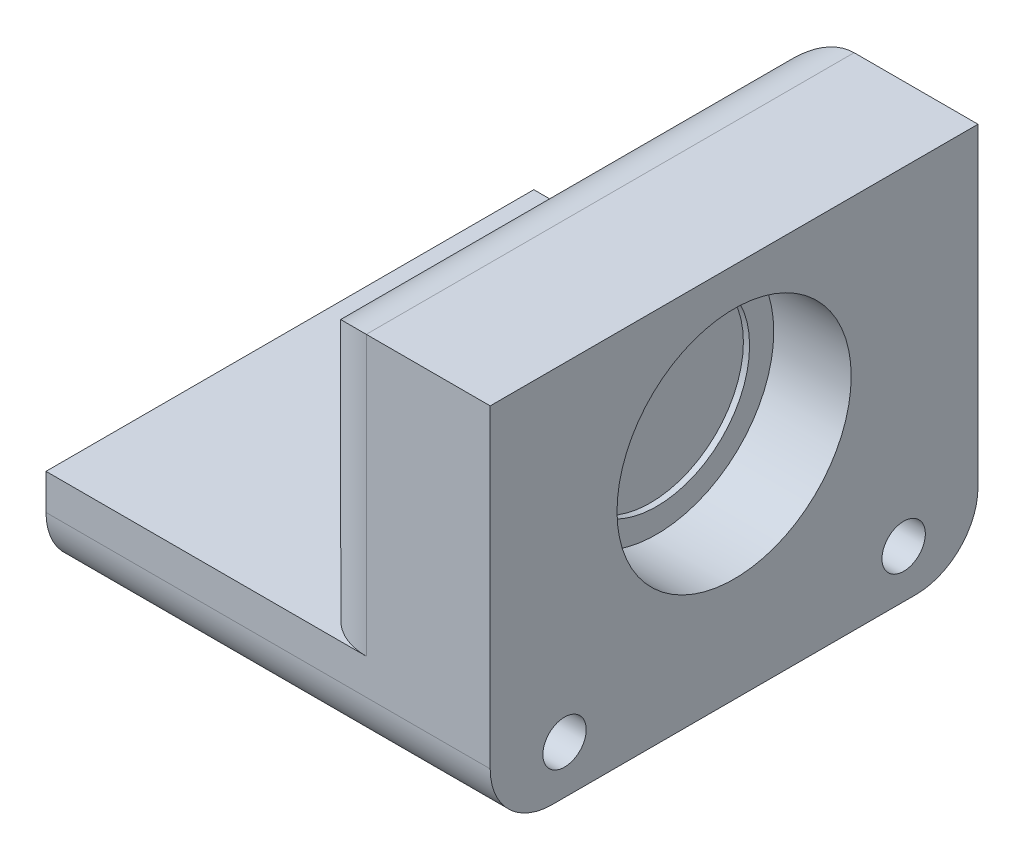
SolidWorks part; units mm, degrees
ref_plane "Front Plane" through (0, 0, 0) normal (0, 0, 1) x (1, 0, 0)
ref_plane "Top Plane" through (0, 0, 0) normal (0, 1, 0) x (1, 0, 0)
ref_plane "Right Plane" through (0, 0, 0) normal (1, 0, 0) x (0, 0, -1)
sketch "Sketch1" plane through (0, 0, 0) normal (0, 0, 1) x (1, 0, 0)
  line L0 (-71.7423, 0) -> (-71.7423, -4)
  line L1 (-71.7423, -4) -> (-53.5305, -4)
  line L2 (-53.5305, -4) -> (-53.5305, 11.43)
  line L3 (-53.5305, 11.43) -> (-61.1505, 11.43)
  line L4 (-61.1505, 11.43) -> (-61.1505, 0)
  line L5 (-61.1505, 0) -> (-71.7423, 0)
  dimension "D1" = 4
  dimension "D2" = 18.2118
  dimension "D3" = 15.43
  dimension "D4" = 10.5918
extrude "Boss-Extrude1" add sketch "Sketch1" against normal blind 20
sketch "Sketch2" plane through (-71.7423, 0, 0) normal (-1, 0, 0) x (0, 0, 1)
  line L0 (-10, 0) -> (-10, -4) construction
  line L1 (-20, 0) -> (0, 0) construction
  line L2 (-20, -4) -> (0, -4) construction
  line L3 (-20, -2) -> (0, -2) construction
  line L4 (-20, 0) -> (-20, -4) construction
  line L5 (0, 0) -> (0, -4) construction
  circle A0 centre (-12.286, -2) radius 1.27
  circle A1 centre (-7.714, -2) radius 1.27
  dimension "D1" = 2.54
  dimension "D2" = 2.286
extrude "Cut-Extrude1" cut sketch "Sketch2" against normal blind 4
sketch "Sketch3" plane through (-61.1505, 0, 0) normal (-1, 0, 0) x (0, 0, 1)
  line L0 (-10, 11.43) -> (-10, 0) construction
  line L1 (-20, 11.43) -> (0, 11.43) construction
  line L2 (-20, 0) -> (0, 0) construction
  circle A0 centre (-10, 5.08) radius 4.8006
  dimension "D1" = 5.08
extrude "Cut-Extrude2" cut sketch "Sketch3" against normal blind 3.175 contours A0
sketch "Sketch4" plane through (-57.9755, 0, 0) normal (-1, 0, 0) x (0, 0, 1)
  circle A0 centre (-10, 5.08) radius 3.81
extrude "Cut-Extrude3" cut sketch "Sketch4" against normal blind 0.254
sketch "Sketch5" plane through (-53.5305, 0, 0) normal (1, 0, 0) x (0, 0, -1)
  line L0 (0, 0) -> (20, 0) construction
  line L1 (10, 11.43) -> (10, 0) construction
  line L2 (20, 11.43) -> (0, 11.43) construction
  circle A0 centre (10, 5.08) radius 4.8006
  dimension "D2" = 9.6012
  dimension "D1" = 5.08
extrude "Cut-Extrude4" cut sketch "Sketch5" against normal blind 3.175
sketch "Sketch6" plane through (-56.7055, 0, 0) normal (1, 0, 0) x (0, 0, -1)
  circle A0 centre (10, 5.08) radius 3.81
extrude "Cut-Extrude5" cut sketch "Sketch6" against normal blind 0.254
sketch "Sketch7" plane through (-67.7423, 0, 0) normal (-1, 0, 0) x (0, 0, 1)
  line L0 (-20, 0) -> (0, 0) construction
  line L1 (-20, 0) -> (-20, -4) construction
  line L2 (-10, 0) -> (-10, -4) construction
  line L3 (-20, -4) -> (0, -4) construction
  point P0 (-16.952, -2.032)
  point P9 (-3.048, -2.032)
  dimension "D1" = 2.032
  dimension "D2" = 3.048
hole_wizard "CBORE for #0 Socket Head Cap Screw1" positions "Sketch9" profile "Sketch8" counterbore size "#0" standard "ANSI Inch" end condition through all
sketch "Sketch9" plane through (-71.7423, 0, 0) normal (-1, 0, 0) x (0, 0, 1)
  point P0 (-16.952, -2.032)
  point P3 (-3.048, -2.032)
sketch "Sketch8" plane through (-71.7423, -2.032, -16.952) normal (0, 1, 0) x (0, 0, 1)
  line L0 (0, 0) -> (0, 18.2118)
  line L1 (0, 18.2118) -> (0.889, 18.2118)
  line L3 (0.889, 18.2118) -> (0.889, 14.732)
  line L4 (0.889, 14.732) -> (1.5875, 14.732)
  line L5 (1.5875, 14.732) -> (1.5875, 0)
  line L7 (1.5875, 0) -> (0, 0)
  line L11 (0, -6.35) -> (0, 107.95) construction
  dimension "Thru Hole Dia." = 1.778
  dimension "Thru Hole Depth" = 18.2118
  dimension "C'Bore Dia." = 3.175
  dimension "C'Bore Depth" = 14.732
fillet "Fillet1" radius 2.54 5 edges at (-61.1505, 5.715, -20) (-61.1505, 11.43, -10) (-61.1505, 5.715, 0) (-62.6364, -4, 0) (-62.6364, -4, -20)
sketch "Sketch10" plane through (0, -4, 0) normal (0, -1, 0) x (1, 0, 0)
  line L0 (-71.7423, -10) -> (-64.4923, -10) construction
  line L1 (-71.7423, -17.46) -> (-71.7423, -2.54) construction
  circle A0 centre (-64.4923, -7.25) radius 1.2635
  circle A1 centre (-64.4923, -12.75) radius 1.2635
  point P4 (-64.4923, -7.25)
  point P5 (-64.4923, -12.75)
  dimension "D3" = 2.527
  dimension "D1" = 2.75
  dimension "D2" = 7.25
extrude "Cut-Extrude6" cut sketch "Sketch10" against normal through all
